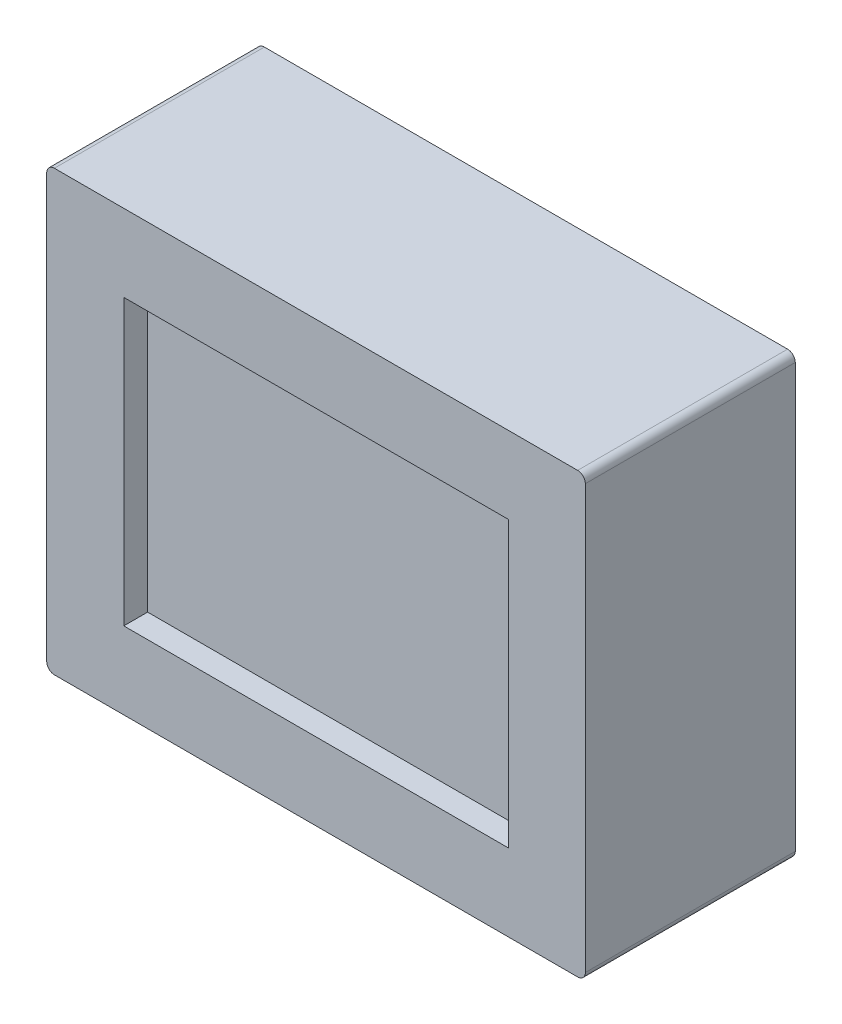
SolidWorks part; units mm, degrees
material "A-Glass Fiber"
ref_plane "Front Plane" through (0, 0, 0) normal (0, 0, 1) x (1, 0, 0)
ref_plane "Top Plane" through (0, 0, 0) normal (0, 1, 0) x (1, 0, 0)
ref_plane "Right Plane" through (0, 0, 0) normal (1, 0, 0) x (0, 0, -1)
sketch "main_features_sketch" plane through (0, 0, 0) normal (0, 0, 1) x (1, 0, 0)
  line L0 (-20, -28.525) -> (-20, -38.525)
  line L1 (35.02, 28.525) -> (-35.02, 28.525)
  line L2 (35.02, 28.525) -> (35.02, -28.525)
  line L3 (35.02, -28.525) -> (-35.02, -28.525)
  line L4 (-35.02, 28.525) -> (-35.02, -28.525)
  line L5 (0, -28.525) -> (0, 28.525) construction
  line L6 (35.02, 0) -> (-35.02, 0) construction
  line L7 (25, 18.5) -> (-25, 18.5)
  line L8 (25, 18.5) -> (25, -18.5)
  line L9 (25, -18.5) -> (-25, -18.5)
  line L10 (-25, 18.5) -> (-25, -18.5)
  line L11 (25, 18.5) -> (-25, -18.5) construction
  line L12 (25, -18.5) -> (-25, 18.5) construction
  line L13 (-20, -38.525) -> (-16, -38.525)
  line L14 (-16, -38.525) -> (-16, -28.525)
  line L15 (16, -38.525) -> (16, -28.525)
  line L16 (20, -38.525) -> (16, -38.525)
  line L17 (20, -28.525) -> (20, -38.525)
  line L19 (32, 25.5) -> (-32, 25.5) construction
  line L20 (32, 25.5) -> (32, -25.5) construction
  line L21 (32, -25.5) -> (-32, -25.5) construction
  line L22 (-32, 25.5) -> (-32, -25.5) construction
  line L23 (32, 25.5) -> (-32, -25.5) construction
  line L24 (32, -25.5) -> (-32, 25.5) construction
  circle A0 centre (-32, -25.5) radius 2.25
  circle A1 centre (-32, 25.5) radius 2.25
  circle A2 centre (32, 25.5) radius 2.25
  circle A3 centre (32, -25.5) radius 2.25
  point P0 (0, 0)
  point P4 (0, 0)
  point P17 (-18, -38.525)
  point P18 (18, -38.525)
  point P19 (0, 0)
  dimension "D8" = 4.5
  dimension "D1" = 4
  dimension "D2" = 70.04
  dimension "D3" = 57.05
  dimension "D4" = 50
  dimension "D5" = 37
  dimension "D6" = 36
  dimension "D7" = 10
  dimension "D9" = 51
  dimension "D10" = 64
extrude "main_body" add sketch "main_features_sketch" along normal blind 27.3 contours L4 L3 L2 L1
extrude "wires" add sketch "main_features_sketch<3>" along normal blind 4 from offset 2.1 contours L13 L14 L3 L0 | L17 L3 L15 L16 region at (-18, -33.525, 0) region at (18, -33.525, 0)
sketch "main_features_sketch<3>" plane through (0, 0, 0) normal (0, 0, 1) x (1, 0, 0) same geometry as "main_features_sketch"
extrude "lens_cutout" cut sketch "main_features_sketch<4>" against normal blind 3.1 from surface contours L7 L10 L9 L8 region at (0, 0, 0) starting at face at (0, 0, 27.3)
sketch "main_features_sketch<4>" plane through (0, 0, 0) normal (0, 0, 1) x (1, 0, 0) same geometry as "main_features_sketch"
extrude "screw_heads" add sketch "main_features_sketch<5>" against normal blind 0.3 contours A0 | A3 | A2 | A1 region at (-32, -25.5, 0) region at (-32, 25.5, 0) region at (32, 25.5, 0) region at (32, -25.5, 0)
sketch "main_features_sketch<5>" plane through (0, 0, 0) normal (0, 0, 1) x (1, 0, 0) same geometry as "main_features_sketch"
fillet "Fillet1" radius 1 4 edges at (-35.02, 28.525, 13.65) (35.02, 28.525, 13.65) (35.02, -28.525, 13.65) (-35.02, -28.525, 13.65)
fillet "Fillet2" radius 2 8 edges at (20, -33.525, 2.1) (20, -33.525, 6.1) (16, -33.525, 2.1) (16, -33.525, 6.1) (-16, -33.525, 2.1) (-16, -33.525, 6.1) (-20, -33.525, 2.1) (-20, -33.525, 6.1)
ref_plane "emitting_plane" through (0, 0, 24.2) normal (0, 0, 1) x (1, 0, 0)
ref_axis "emitting_axis" through (0, 0, 22.2837) along (0, 0, 1)
